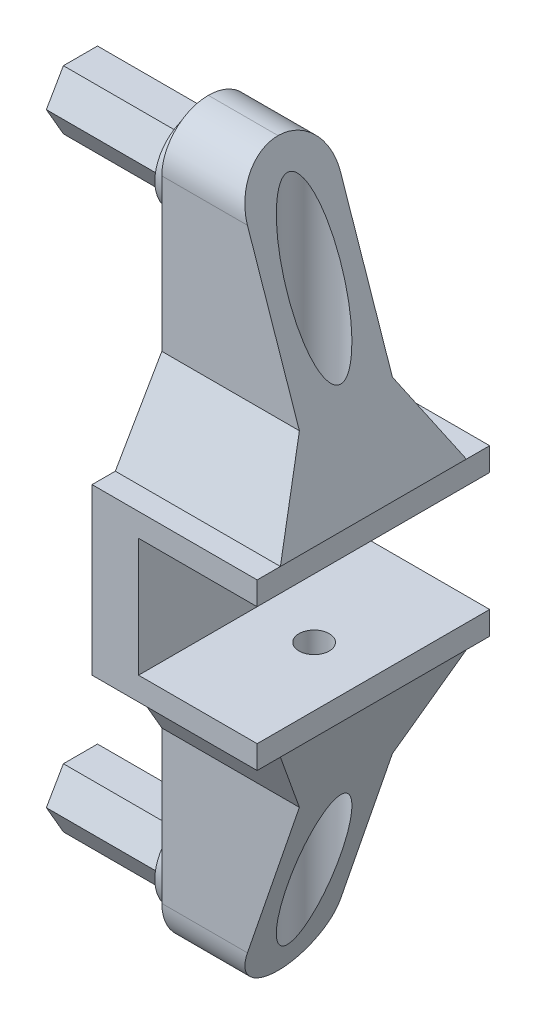
SolidWorks part; units mm, degrees
material "PETG"
ref_plane "Front Plane" through (0, 0, 0) normal (0, 0, 1) x (1, 0, 0)
ref_plane "Top Plane" through (0, 0, 0) normal (0, 1, 0) x (1, 0, 0)
ref_plane "Right Plane" through (0, 0, 0) normal (1, 0, 0) x (0, 0, -1)
sketch "Sketch1" plane through (0, 0, 0) normal (0, 0, 1) x (1, 0, 0)
  line L0 (25.5, -12.75) -> (25.5, -17.75)
  line L1 (0, -12.75) -> (25.5, -12.75)
  line L2 (0, -12.75) -> (0, 12.75)
  line L3 (0, 12.75) -> (25.5, 12.75)
  line L5 (-5, 17.75) -> (25.5, 17.75)
  line L6 (-5, 17.75) -> (-5, -17.75)
  line L7 (-5, -17.75) -> (25.5, -17.75)
  line L8 (25.5, 17.75) -> (25.5, 12.75)
  dimension "D1" = 25.5
  dimension "D2" = 5
  dimension "D3" = 5
extrude "Boss-Extrude1" add sketch "Sketch1" along normal mid plane 50
sketch "Sketch2" plane through (0, 0, 0) normal (0, 0, 1) x (1, 0, 0)
  line L0 (-5, 17.75) -> (-5, 77.75)
  line L2 (25.5, 17.75) -> (-5, 17.75)
  line L3 (0, 0) -> (50000, 0) construction
  line L7 (25.5, 17.75) -> (5, 77.75)
  line L8 (5, 77.75) -> (-5, 77.75)
  line L9 (5, -77.75) -> (-5, -77.75)
  line L10 (25.5, -17.75) -> (5, -77.75)
  line L11 (25.5, -17.75) -> (-5, -17.75)
  line L12 (-5, -17.75) -> (-5, -77.75)
  dimension "D1" = 60
  dimension "D2" = 10
extrude "Boss-Extrude2" add sketch "Sketch2" along normal mid plane 20
sketch "Sketch8" plane through (-5, 0, 0) normal (-1, 0, 0) x (0, 0, 1)
  line L0 (10, 17.75) -> (25, 17.75)
  line L1 (-25, 17.75) -> (-10, 17.75)
  line L2 (-25, 17.75) -> (-25, -17.75)
  line L3 (-25, -17.75) -> (-10, -17.75)
  line L4 (25, 17.75) -> (25, -17.75)
  line L5 (-10, 77.75) -> (10, 77.75)
  line L6 (-10, 77.75) -> (-10, 17.75)
  line L7 (-10, -77.75) -> (10, -77.75)
  line L8 (10, 77.75) -> (10, 17.75)
  line L9 (10, -17.75) -> (25, -17.75)
  line L10 (10, -17.75) -> (10, -77.75)
  line L11 (-10, -17.75) -> (-10, -77.75)
extrude "Boss-Extrude7" add sketch "Sketch8" along normal blind 5
sketch "Sketch4" plane through (-10, 0, 0) normal (-1, 0, 0) x (0, 0, 1)
  line L12 (0, 65) -> (0, -65) construction
  circle A0 centre (0, 65) radius 9
  circle A1 centre (0, -65) radius 9
  dimension "D1" = 18
  dimension "D2" = 130
extrude "Boss-Extrude4" add sketch "Sketch4" along normal blind 2.5
sketch "Sketch6" plane through (-12.5, 0, 0) normal (-1, 0, 0) x (0, 0, 1)
  line L1 (7.3323, 65) -> (3.6662, 71.35)
  line L2 (3.6662, 71.35) -> (-3.6662, 71.35)
  line L3 (-3.6662, 71.35) -> (-7.3323, 65)
  line L4 (-7.3323, 65) -> (-3.6662, 58.65)
  line L5 (-3.6662, 58.65) -> (3.6662, 58.65)
  line L6 (3.6662, 58.65) -> (7.3323, 65)
  line L7 (7.3323, -65) -> (3.6662, -58.65)
  line L8 (3.6662, -58.65) -> (-3.6662, -58.65)
  line L9 (-3.6662, -58.65) -> (-7.3323, -65)
  line L10 (-7.3323, -65) -> (-3.6662, -71.35)
  line L11 (-3.6662, -71.35) -> (3.6662, -71.35)
  line L12 (3.6662, -71.35) -> (7.3323, -65)
  circle A0 centre (0, 65) radius 6.35 construction
  circle A1 centre (0, -65) radius 6.35 construction
  circle A2 centre (0, 65) radius 9 construction
  circle A3 centre (0, -65) radius 9 construction
  dimension "D1" = 12.7
extrude "Boss-Extrude6" add sketch "Sketch6" along normal blind 25
sketch "Sketch7" plane through (-37.5, 0, 0) normal (-1, 0, 0) x (0, 0, 1)
  circle A0 centre (0, 65) radius 2
  circle A1 centre (0, 65) radius 9 construction
  circle A2 centre (0, -65) radius 2
  circle A4 centre (0, -65) radius 9 construction
  dimension "D1" = 4
extrude "Cut-Extrude1" cut sketch "Sketch7" against normal blind 12
fillet "Fillet1" radius 10 4 edges at (-2.5, -77.75, -10) (-2.5, -77.75, 10) (-2.5, 77.75, -10) (-2.5, 77.75, 10)
chamfer "Chamfer1" distance 10 angle 60 4 edges at (7.75, -17.75, 10) (7.75, -17.75, -10) (7.75, 17.75, -10) (7.75, 17.75, 10)
sketch "Sketch9" plane through (0, 0, 0) normal (0, 1, 0) x (1, 0, 0)
  line L3 (0, 0) -> (25.5, 0) construction
  line L4 (25.5, -20) -> (25.5, 20) construction
  circle A0 centre (12.75, 0) radius 3.25
  dimension "D1" = 6.5
extrude "Cut-Extrude2" cut sketch "Sketch9" against normal through all both and the other way through all
ref_plane "Plane1" through (0, -22.75, 0) normal (0, 1, 0) x (1, 0, 0)
sketch "Sketch10" plane through (0, -22.75, 0) normal (0, 1, 0) x (1, 0, 0)
  circle A0 centre (12.75, 0) radius 5.75
  circle A1 centre (12.75, 0) radius 3.25 construction
  dimension "D1" = 11.5
extrude "Cut-Extrude3" cut sketch "Sketch10" against normal through all
mirror "Mirror1" about plane through (0, 0, 0) normal (0, 1, 0) of "Cut-Extrude3"
equation "\"tol_dia_id_intfc\" = 0.0500mm ' For hole diameters - Interference fit"
equation "\"tol_dia_id_slip\"  = 0.0750mm ' For hole diameters - Slip fit"
equation "\"tol_dia_id_clear\" = 0.1000mm ' For hole diameters - Clearance fit"
equation "\"tol_dia_od_intfc\" = 0.0500mm ' For shaft diameters - Interference fit"
equation "\"tol_dia_od_slip\"  = 0.0750mm ' For shaft diameters - Slip fit"
equation "\"tol_dia_od_clear\" = 0.1000mm ' For shaft diameters - Clearance fit"
equation "\"tol_general_intfc\"= 0.0250mm ' For general parts (Horiz) - Interference fit"
equation "\"tol_general_slip\" = 0.0375mm ' For general parts (Horiz) - Slip fit"
equation "\"tol_general_clear\"= 0.0500mm ' For general parts (Horiz) - Clearance fit"
equation "\"tol_layer_intfc\"  = 0.0250mm ' For all parts (Vert) - Interference fit"
equation "\"tol_layer_slip\"   = 0.0375mm ' For all parts (Vert) - Slip fit"
equation "\"tol_layer_clear\"  = 0.0500mm ' For all parts (Vert) - Clearance fit"
equation "\"tol_corner_rad\"   = 0.100mm ' For corners that fit into other parts"
equation "\"D1@Sketch1\"=1in + \"tol_general_clear\"*2"
equation "\"D3@Sketch1\"=\"D2@Sketch1\""
equation "\"D1@Sketch7\"=3.95mm + \"tol_dia_id_intfc\""
